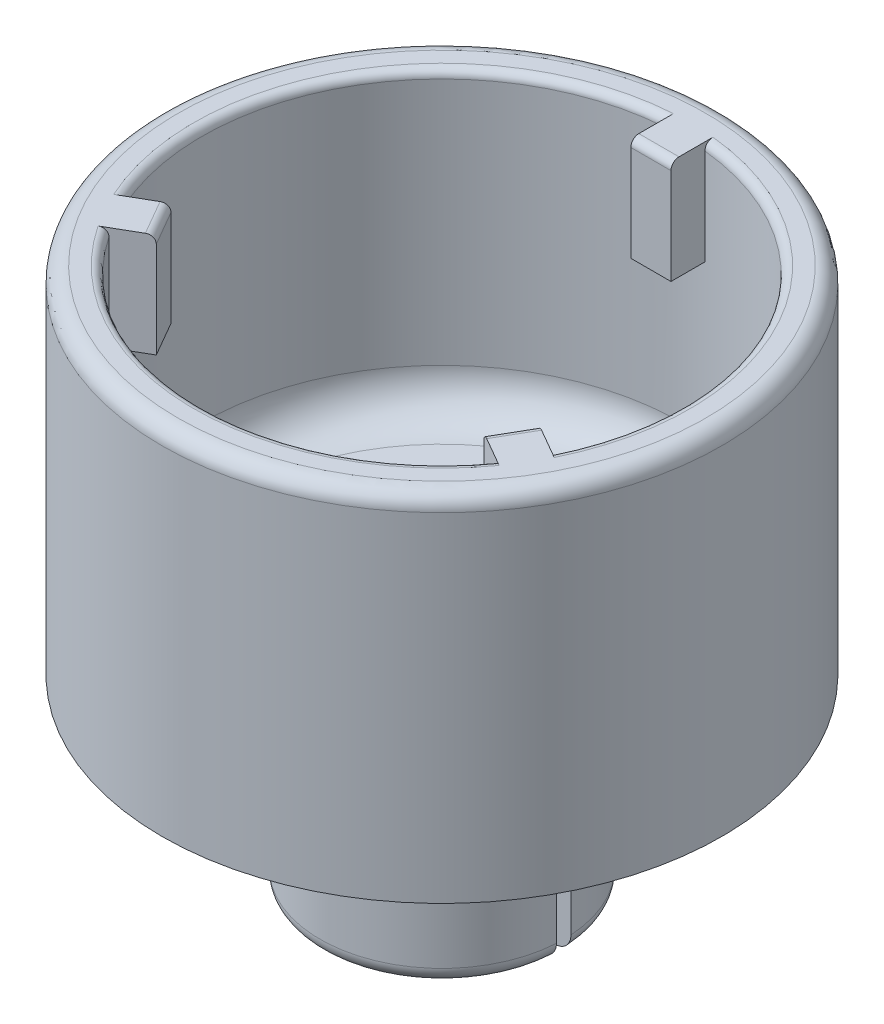
SolidWorks part; units mm, degrees
ref_plane "Front Plane" through (0, 0, 0) normal (0, 0, 1) x (1, 0, 0)
ref_plane "Top Plane" through (0, 0, 0) normal (0, 1, 0) x (1, 0, 0)
ref_plane "Right Plane" through (0, 0, 0) normal (1, 0, 0) x (0, 0, -1)
sketch "Sketch1" plane through (0, 0, 0) normal (0, 1, 0) x (1, 0, 0)
  circle A0 centre (0, 0) radius 35
  dimension "D1" = 70
extrude "Boss-Extrude1" add sketch "Sketch1" along normal blind 44.3
sketch "Sketch2" plane through (0, 44.3, 0) normal (0, 1, 0) x (1, 0, 0)
  circle A0 centre (0, 0) radius 30
  dimension "D1" = 60
extrude "Cut-Extrude1" cut sketch "Sketch2" against normal blind 37
sketch "Sketch3" plane through (0, 0, 0) normal (0, -1, 0) x (1, 0, 0)
  circle A0 centre (0, 0) radius 19.5
  dimension "D1" = 39
extrude "Boss-Extrude2" add sketch "Sketch3" along normal blind 7
sketch "Sketch4" plane through (0, -7, 0) normal (0, -1, 0) x (1, 0, 0)
  circle A0 centre (0, 0) radius 15.25
  dimension "D1" = 30.5
extrude "Boss-Extrude3" add sketch "Sketch4" along normal blind 16
fillet "Fillet1" radius 5 1 edges at (0, 0, -19.5)
sketch "Sketch5" plane through (0, 44.3, 0) normal (0, 1, 0) x (1, 0, 0)
  line L0 (-1.9905, 29.9339) -> (-1.9905, 25.6053)
  line L1 (-1.9905, 25.6053) -> (3.0302, 25.6053)
  line L2 (3.0302, 25.6053) -> (3.0302, 29.8466)
  line L3 (26.9188, -13.2431) -> (23.1701, -11.0788)
  line L4 (23.1701, -11.0788) -> (20.6597, -15.4269)
  line L5 (20.6597, -15.4269) -> (24.3328, -17.5475)
  line L6 (-24.9282, -16.6908) -> (-21.1796, -14.5265)
  line L7 (-21.1796, -14.5265) -> (-23.69, -10.1784)
  line L8 (-23.69, -10.1784) -> (-27.363, -12.299)
  circle A0 centre (0, 0) radius 30 construction
  arc A1 (24.3328, -17.5475) -> (26.9188, -13.2431) centre (0, 0) ccw
  circle A2 centre (0, 0) radius 30
  arc A3 (3.0302, 29.8466) -> (-1.9905, 29.9339) centre (0, 0) ccw
  arc A4 (-27.363, -12.299) -> (-24.9282, -16.6908) centre (0, 0) ccw
  point P19 (0, 0)
  dimension "D1" = 0
  dimension "D2" = 3
extrude "Boss-Extrude4" add sketch "Sketch5" against normal blind 13
sketch "Sketch7" plane through (0, -23, 0) normal (0, -1, 0) x (1, 0, 0)
  line L1 (33.0968, 0.9034) -> (-33.0968, 0.9034)
  line L2 (33.0968, 0.9034) -> (33.0968, -0.9034)
  line L3 (33.0968, -0.9034) -> (-33.0968, -0.9034)
  line L4 (-33.0968, 0.9034) -> (-33.0968, -0.9034)
  line L5 (33.0968, 0.9034) -> (-33.0968, -0.9034) construction
  line L6 (33.0968, -0.9034) -> (-33.0968, 0.9034) construction
  point P0 (0, 0)
extrude "Cut-Extrude2" cut sketch "Sketch7" against normal up to surface (16 mm away) up to face at (0, -7, -15.25)
fillet "Fillet2" radius 2 2 edges at (0, -23, 15.25) (0, -23, -15.25)
sketch "Sketch8" plane through (0, 7.3, 0) normal (0, 1, 0) x (1, 0, 0)
  circle A0 centre (0, 0) radius 10.3601
fillet "Fillet3" radius 5 1 edges at (0, 7.3, 30)
fillet "Fillet4" radius 2 1 edges at (0, 44.3, 35)
fillet "Fillet5" radius 1 3 edges at (-0.5217, 44.3, 29.9955) (26.2377, 44.3, -14.5459) (-25.716, 44.3, -15.4495)
fillet "Fillet6" radius 1 3 edges at (21.9149, 44.3, 13.2529) (-22.4348, 44.3, 12.3525) (0.5198, 44.3, -25.6053)
